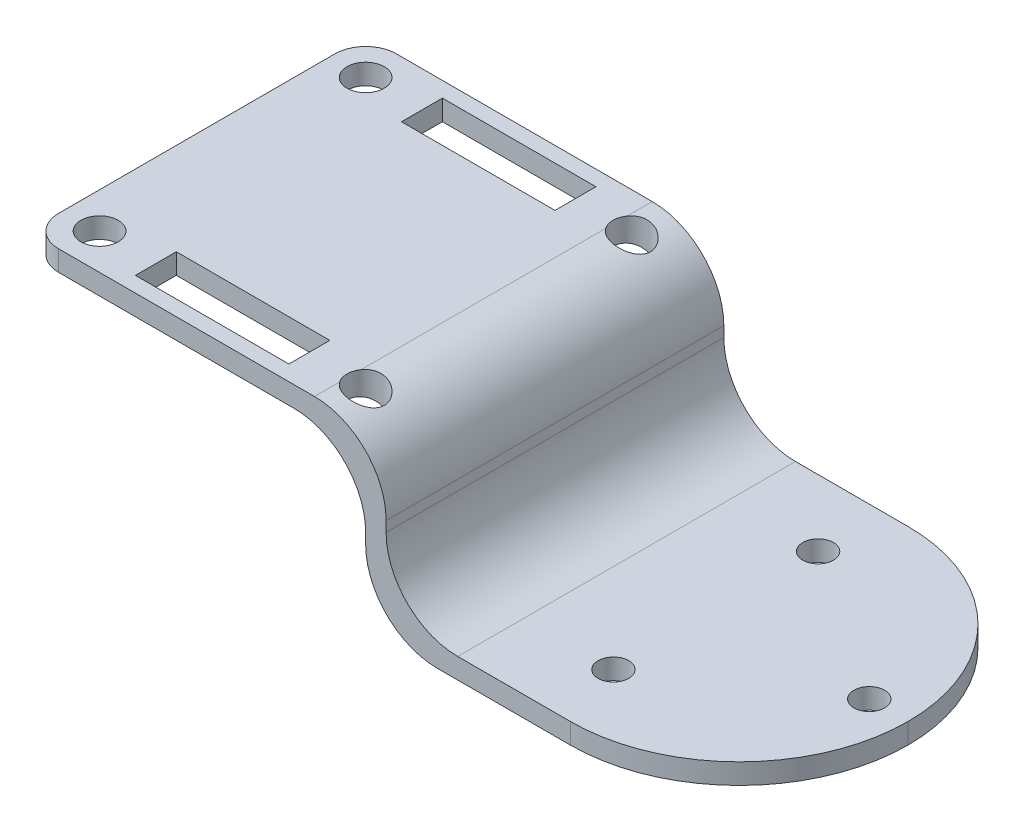
SolidWorks part; units mm, degrees
ref_plane "Plan de face" through (0, 0, 0) normal (0, 0, 1) x (1, 0, 0)
ref_plane "Plan de dessus" through (0, 0, 0) normal (0, 1, 0) x (1, 0, 0)
ref_plane "Plan de droite" through (0, 0, 0) normal (1, 0, 0) x (0, 0, -1)
sketch "Sketch1" plane through (0, 0, 0) normal (0, 1, 0) x (1, 0, 0)
  line L0 (-55, 0) -> (55, 0) construction
  line L1 (-16.5, 16.5) -> (16.5, 16.5)
  line L2 (-16.5, 16.5) -> (-16.5, -16.5)
  line L3 (-16.5, -16.5) -> (16.5, -16.5)
  line L4 (16.5, 16.5) -> (16.5, -16.5)
  line L5 (-13, 13) -> (13, 13) construction
  line L6 (-13, 13) -> (-13, -13) construction
  line L7 (-13, -13) -> (13, -13) construction
  line L8 (13, 13) -> (13, -13) construction
  line L9 (-7.5, 15) -> (7.5, 15)
  line L10 (-7.5, 15) -> (-7.5, 11)
  line L11 (-7.5, 11) -> (7.5, 11)
  line L12 (7.5, 15) -> (7.5, 11)
  line L13 (-7.5, -11) -> (7.5, -11)
  line L14 (7.5, -15) -> (7.5, -11)
  line L15 (-7.5, -15) -> (7.5, -15)
  line L16 (-7.5, -15) -> (-7.5, -11)
  line L18 (16.5, -16.5) -> (18.5, -16.5)
  line L19 (16.5, -16.5) -> (16.5, 16.5)
  line L20 (16.5, 16.5) -> (18.5, 16.5)
  line L21 (18.5, -16.5) -> (18.5, 16.5)
  circle A0 centre (-13, 13) radius 1.8246
  circle A1 centre (13, 13) radius 1.8246
  circle A2 centre (13, -13) radius 1.8246
  circle A3 centre (-13, -13) radius 1.8246
  point P4 (-16.5, 0)
  point P6 (0, 16.5)
  point P11 (0, 13)
  point P12 (-13, 0)
  point P24 (7.5, 13)
  point P25 (0, 11)
  dimension "D5" = 3.6493
  dimension "D1" = 33
  dimension "D2" = 33
  dimension "D3" = 26
  dimension "D4" = 26
  dimension "D7" = 15
  dimension "D8" = 4
  dimension "D9" = 2
  dimension "D6" = 4
extrude "Boss-Extrude1" add sketch "Sketch1" along normal blind 2 contours L4 L1 L2 L3 A3 A2 A1 A0 L9 L12 L11 L10 L15 L16 L13 L14 region at (0, 0, 0)
ref_plane "Plane1" through (0, -15, 0) normal (0, 1, 0) x (1, 0, 0)
sketch "Sketch2" plane through (0, -15, 0) normal (0, 1, 0) x (1, 0, 0)
  line L0 (-1.1, 0) -> (1.1, 0) construction
  line L1 (16.5, 16.5) -> (53.0013, 16.5)
  line L2 (16.5, 16.5) -> (16.5, -16.5)
  line L3 (16.5, -16.5) -> (53.0013, -16.5)
  line L4 (53.0013, 16.5) -> (53.0013, -16.5)
  circle A0 centre (34.2102, 10) radius 1.5
  circle A2 centre (49.2102, 0) radius 1.5
  circle A3 centre (34.2102, -10) radius 1.5
  dimension "D1" = 3
  dimension "D2" = 15
  dimension "D3" = 3
  dimension "D4" = 33
  dimension "D5" = 10
extrude "Boss-Extrude2" add sketch "Sketch2" along normal blind 2 separate body contours L4 L1 L2 L3 A2 A0 region at (34.6708, -15, 0)
extrude "Boss-Extrude3" add sketch "Sketch1<3>" along normal blind 2 and the other way up to surface (13 mm away) contours L18 L21 L20 L4 region at (17.5, 0, 0) other way up to face at (34.7507, -13, 0)
sketch "Sketch1<3>" plane through (0, 0, 0) normal (0, 1, 0) x (1, 0, 0) same geometry as "Sketch1"
fillet "Fillet1" radius 7 4 edges at (16.5, 0, 0) (18.5, -13, 0) (16.5, -15, 0) (18.5, 2, 0)
fillet "Fillet2" radius 16.5 2 edges at (53.0013, -14, -16.5) (53.0013, -14, 16.5)
fillet "Fillet3" radius 3 2 edges at (-16.5, 1, 16.5) (-16.5, 1, -16.5)
equation "\"1§\"=15.5"
